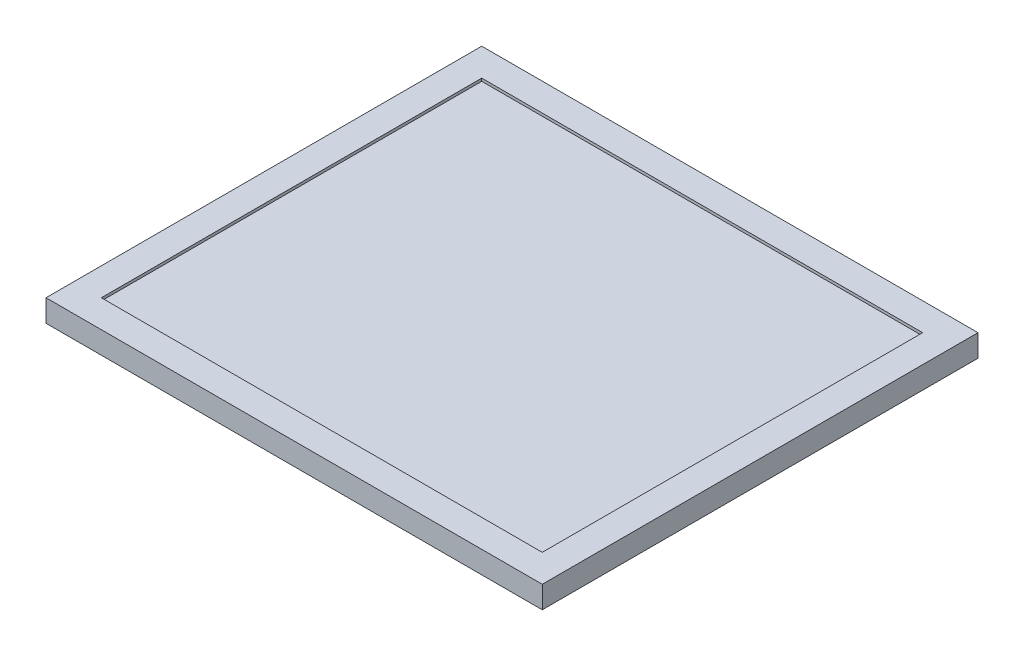
SolidWorks part; units mm, degrees
ref_plane "Front" through (0, 0, 0) normal (0, 0, 1) x (1, 0, 0)
ref_plane "Top" through (0, 0, 0) normal (0, 1, 0) x (1, 0, 0)
ref_plane "Right" through (0, 0, 0) normal (1, 0, 0) x (0, 0, -1)
sketch "Sketch1" plane through (0, 0, 0) normal (0, 1, 0) x (1, 0, 0)
  line L0 (-328.7092, 295) -> (-338.75, 284.9592)
  line L1 (348.75, 305) -> (-348.75, 305)
  line L2 (348.75, 305) -> (348.75, -305)
  line L4 (-348.75, 305) -> (-348.75, -305)
  line L5 (0, -305) -> (0, 305) construction
  line L6 (348.75, 0) -> (-348.75, 0) construction
  line L7 (-328.7092, 295) -> (-318.7092, 295)
  line L8 (-338.75, 284.9592) -> (-338.75, 227.4386)
  line L9 (-329.0717, 217.7603) -> (-318.7092, 217.7603)
  line L10 (-256.2915, 285.3217) -> (-256.2915, 227.4386)
  line L11 (-265.9698, 295) -> (-256.2915, 285.3217)
  line L12 (-256.2915, 227.4386) -> (-265.9698, 217.7603)
  line L13 (-338.75, 227.4386) -> (-329.0717, 217.7603)
  line L14 (-297.5208, 295) -> (-297.5208, 217.7603) construction
  line L15 (-318.7092, 295) -> (-318.7092, 217.7603)
  line L16 (-315.7092, 295) -> (-315.7092, 217.7603)
  line L17 (-276.3323, 295) -> (-276.3323, 217.7603)
  line L18 (-279.3323, 295) -> (-279.3323, 217.7603)
  line L19 (-315.7092, 295) -> (-279.3323, 295)
  line L20 (-276.3323, 295) -> (-265.9698, 295)
  line L21 (-276.3323, 217.7603) -> (-265.9698, 217.7603)
  line L22 (-315.7092, 217.7603) -> (-279.3323, 217.7603)
  line L23 (-253.75, 284.9592) -> (-253.75, 227.4386)
  line L24 (-253.75, 227.4386) -> (-244.0717, 217.7603)
  line L25 (-244.0717, 217.7603) -> (-233.7092, 217.7603)
  line L26 (-233.7092, 295) -> (-233.7092, 217.7603)
  line L27 (-243.7092, 295) -> (-233.7092, 295)
  line L28 (-243.7092, 295) -> (-253.75, 284.9592)
  line L29 (-194.3323, 295) -> (-194.3323, 217.7603)
  line L30 (-230.7092, 217.7603) -> (-194.3323, 217.7603)
  line L31 (-230.7092, 295) -> (-230.7092, 217.7603)
  line L32 (-230.7092, 295) -> (-194.3323, 295)
  line L33 (-191.3323, 295) -> (-191.3323, 217.7603)
  line L34 (-191.3323, 217.7603) -> (-180.9698, 217.7603)
  line L35 (-171.2915, 227.4386) -> (-180.9698, 217.7603)
  line L36 (-171.2915, 285.3217) -> (-171.2915, 227.4386)
  line L37 (-180.9698, 295) -> (-171.2915, 285.3217)
  line L38 (-191.3323, 295) -> (-180.9698, 295)
  line L39 (-168.75, 284.9592) -> (-168.75, 227.4386)
  line L40 (-168.75, 227.4386) -> (-159.0717, 217.7603)
  line L41 (-159.0717, 217.7603) -> (-148.7092, 217.7603)
  line L42 (-148.7092, 295) -> (-148.7092, 217.7603)
  line L43 (-158.7092, 295) -> (-148.7092, 295)
  line L44 (-158.7092, 295) -> (-168.75, 284.9592)
  line L45 (-109.3323, 295) -> (-109.3323, 217.7603)
  line L46 (-145.7092, 217.7603) -> (-109.3323, 217.7603)
  line L47 (-145.7092, 295) -> (-145.7092, 217.7603)
  line L48 (-145.7092, 295) -> (-109.3323, 295)
  line L49 (-106.3323, 295) -> (-106.3323, 217.7603)
  line L50 (-106.3323, 217.7603) -> (-95.9698, 217.7603)
  line L51 (-86.2915, 227.4386) -> (-95.9698, 217.7603)
  line L52 (-86.2915, 285.3217) -> (-86.2915, 227.4386)
  line L53 (-95.9698, 295) -> (-86.2915, 285.3217)
  line L54 (-106.3323, 295) -> (-95.9698, 295)
  line L55 (-83.75, 284.9592) -> (-83.75, 227.4386)
  line L56 (-83.75, 227.4386) -> (-74.0717, 217.7603)
  line L57 (-74.0717, 217.7603) -> (-63.7092, 217.7603)
  line L58 (-63.7092, 295) -> (-63.7092, 217.7603)
  line L59 (-73.7092, 295) -> (-63.7092, 295)
  line L60 (-73.7092, 295) -> (-83.75, 284.9592)
  line L61 (-24.3323, 295) -> (-24.3323, 217.7603)
  line L62 (-60.7092, 217.7603) -> (-24.3323, 217.7603)
  line L63 (-60.7092, 295) -> (-60.7092, 217.7603)
  line L64 (-60.7092, 295) -> (-24.3323, 295)
  line L65 (-21.3323, 295) -> (-21.3323, 217.7603)
  line L66 (-21.3323, 217.7603) -> (-10.9698, 217.7603)
  line L67 (-1.2915, 227.4386) -> (-10.9698, 217.7603)
  line L68 (-1.2915, 285.3217) -> (-1.2915, 227.4386)
  line L69 (-10.9698, 295) -> (-1.2915, 285.3217)
  line L70 (-21.3323, 295) -> (-10.9698, 295)
  line L71 (1.25, 284.9592) -> (1.25, 227.4386)
  line L72 (1.25, 227.4386) -> (10.9283, 217.7603)
  line L73 (10.9283, 217.7603) -> (21.2908, 217.7603)
  line L74 (21.2908, 295) -> (21.2908, 217.7603)
  line L75 (11.2908, 295) -> (21.2908, 295)
  line L76 (11.2908, 295) -> (1.25, 284.9592)
  line L77 (60.6677, 295) -> (60.6677, 217.7603)
  line L78 (24.2908, 217.7603) -> (60.6677, 217.7603)
  line L79 (24.2908, 295) -> (24.2908, 217.7603)
  line L80 (24.2908, 295) -> (60.6677, 295)
  line L81 (63.6677, 295) -> (63.6677, 217.7603)
  line L82 (63.6677, 217.7603) -> (74.0302, 217.7603)
  line L83 (83.7085, 227.4386) -> (74.0302, 217.7603)
  line L84 (83.7085, 285.3217) -> (83.7085, 227.4386)
  line L85 (74.0302, 295) -> (83.7085, 285.3217)
  line L86 (63.6677, 295) -> (74.0302, 295)
  line L87 (86.25, 284.9592) -> (86.25, 227.4386)
  line L88 (86.25, 227.4386) -> (95.9283, 217.7603)
  line L89 (95.9283, 217.7603) -> (106.2908, 217.7603)
  line L90 (106.2908, 295) -> (106.2908, 217.7603)
  line L91 (96.2908, 295) -> (106.2908, 295)
  line L92 (96.2908, 295) -> (86.25, 284.9592)
  line L93 (145.6677, 295) -> (145.6677, 217.7603)
  line L94 (109.2908, 217.7603) -> (145.6677, 217.7603)
  line L95 (109.2908, 295) -> (109.2908, 217.7603)
  line L96 (109.2908, 295) -> (145.6677, 295)
  line L97 (148.6677, 295) -> (148.6677, 217.7603)
  line L98 (148.6677, 217.7603) -> (159.0302, 217.7603)
  line L99 (168.7085, 227.4386) -> (159.0302, 217.7603)
  line L100 (168.7085, 285.3217) -> (168.7085, 227.4386)
  line L101 (159.0302, 295) -> (168.7085, 285.3217)
  line L102 (148.6677, 295) -> (159.0302, 295)
  line L103 (171.25, 284.9592) -> (171.25, 227.4386)
  line L104 (171.25, 227.4386) -> (180.9283, 217.7603)
  line L105 (180.9283, 217.7603) -> (191.2908, 217.7603)
  line L106 (191.2908, 295) -> (191.2908, 217.7603)
  line L107 (181.2908, 295) -> (191.2908, 295)
  line L108 (181.2908, 295) -> (171.25, 284.9592)
  line L109 (230.6677, 295) -> (230.6677, 217.7603)
  line L110 (194.2908, 217.7603) -> (230.6677, 217.7603)
  line L111 (194.2908, 295) -> (194.2908, 217.7603)
  line L112 (194.2908, 295) -> (230.6677, 295)
  line L113 (233.6677, 295) -> (233.6677, 217.7603)
  line L114 (233.6677, 217.7603) -> (244.0302, 217.7603)
  line L115 (253.7085, 227.4386) -> (244.0302, 217.7603)
  line L116 (253.7085, 285.3217) -> (253.7085, 227.4386)
  line L117 (244.0302, 295) -> (253.7085, 285.3217)
  line L118 (233.6677, 295) -> (244.0302, 295)
  line L119 (256.25, 284.9592) -> (256.25, 227.4386)
  line L120 (256.25, 227.4386) -> (265.9283, 217.7603)
  line L121 (265.9283, 217.7603) -> (276.2908, 217.7603)
  line L122 (276.2908, 295) -> (276.2908, 217.7603)
  line L123 (266.2908, 295) -> (276.2908, 295)
  line L124 (266.2908, 295) -> (256.25, 284.9592)
  line L125 (315.6677, 295) -> (315.6677, 217.7603)
  line L126 (279.2908, 217.7603) -> (315.6677, 217.7603)
  line L127 (279.2908, 295) -> (279.2908, 217.7603)
  line L128 (279.2908, 295) -> (315.6677, 295)
  line L129 (318.6677, 295) -> (318.6677, 217.7603)
  line L130 (318.6677, 217.7603) -> (329.0302, 217.7603)
  line L131 (338.7085, 227.4386) -> (329.0302, 217.7603)
  line L132 (338.7085, 285.3217) -> (338.7085, 227.4386)
  line L133 (329.0302, 295) -> (338.7085, 285.3217)
  line L134 (318.6677, 295) -> (329.0302, 295)
  line L135 (-253.75, 199.9592) -> (-253.75, 142.4386)
  line L136 (-253.75, 142.4386) -> (-244.0717, 132.7603)
  line L137 (-244.0717, 132.7603) -> (-233.7092, 132.7603)
  line L138 (-233.7092, 210) -> (-233.7092, 132.7603)
  line L139 (-243.7092, 210) -> (-233.7092, 210)
  line L140 (-243.7092, 210) -> (-253.75, 199.9592)
  line L141 (-194.3323, 210) -> (-194.3323, 132.7603)
  line L142 (-230.7092, 132.7603) -> (-194.3323, 132.7603)
  line L143 (-230.7092, 210) -> (-230.7092, 132.7603)
  line L144 (-230.7092, 210) -> (-194.3323, 210)
  line L145 (-191.3323, 210) -> (-191.3323, 132.7603)
  line L146 (-191.3323, 132.7603) -> (-180.9698, 132.7603)
  line L147 (-171.2915, 142.4386) -> (-180.9698, 132.7603)
  line L148 (-171.2915, 200.3217) -> (-171.2915, 142.4386)
  line L149 (-180.9698, 210) -> (-171.2915, 200.3217)
  line L150 (-191.3323, 210) -> (-180.9698, 210)
  line L151 (-168.75, 199.9592) -> (-168.75, 142.4386)
  line L152 (-168.75, 142.4386) -> (-159.0717, 132.7603)
  line L153 (-159.0717, 132.7603) -> (-148.7092, 132.7603)
  line L154 (-148.7092, 210) -> (-148.7092, 132.7603)
  line L155 (-158.7092, 210) -> (-148.7092, 210)
  line L156 (-158.7092, 210) -> (-168.75, 199.9592)
  line L157 (-109.3323, 210) -> (-109.3323, 132.7603)
  line L158 (-145.7092, 132.7603) -> (-109.3323, 132.7603)
  line L159 (-145.7092, 210) -> (-145.7092, 132.7603)
  line L160 (-145.7092, 210) -> (-109.3323, 210)
  line L161 (-106.3323, 210) -> (-106.3323, 132.7603)
  line L162 (-106.3323, 132.7603) -> (-95.9698, 132.7603)
  line L163 (-86.2915, 142.4386) -> (-95.9698, 132.7603)
  line L164 (-86.2915, 200.3217) -> (-86.2915, 142.4386)
  line L165 (-95.9698, 210) -> (-86.2915, 200.3217)
  line L166 (-106.3323, 210) -> (-95.9698, 210)
  line L167 (-83.75, 199.9592) -> (-83.75, 142.4386)
  line L168 (-83.75, 142.4386) -> (-74.0717, 132.7603)
  line L169 (-74.0717, 132.7603) -> (-63.7092, 132.7603)
  line L170 (-63.7092, 210) -> (-63.7092, 132.7603)
  line L171 (-73.7092, 210) -> (-63.7092, 210)
  line L172 (-73.7092, 210) -> (-83.75, 199.9592)
  line L173 (-24.3323, 210) -> (-24.3323, 132.7603)
  line L174 (-60.7092, 132.7603) -> (-24.3323, 132.7603)
  line L175 (-60.7092, 210) -> (-60.7092, 132.7603)
  line L176 (-60.7092, 210) -> (-24.3323, 210)
  line L177 (-21.3323, 210) -> (-21.3323, 132.7603)
  line L178 (-21.3323, 132.7603) -> (-10.9698, 132.7603)
  line L179 (-1.2915, 142.4386) -> (-10.9698, 132.7603)
  line L180 (-1.2915, 200.3217) -> (-1.2915, 142.4386)
  line L181 (-10.9698, 210) -> (-1.2915, 200.3217)
  line L182 (-21.3323, 210) -> (-10.9698, 210)
  line L183 (1.25, 199.9592) -> (1.25, 142.4386)
  line L184 (1.25, 142.4386) -> (10.9283, 132.7603)
  line L185 (10.9283, 132.7603) -> (21.2908, 132.7603)
  line L186 (21.2908, 210) -> (21.2908, 132.7603)
  line L187 (11.2908, 210) -> (21.2908, 210)
  line L188 (11.2908, 210) -> (1.25, 199.9592)
  line L189 (60.6677, 210) -> (60.6677, 132.7603)
  line L190 (24.2908, 132.7603) -> (60.6677, 132.7603)
  line L191 (24.2908, 210) -> (24.2908, 132.7603)
  line L192 (24.2908, 210) -> (60.6677, 210)
  line L193 (63.6677, 210) -> (63.6677, 132.7603)
  line L194 (63.6677, 132.7603) -> (74.0302, 132.7603)
  line L195 (83.7085, 142.4386) -> (74.0302, 132.7603)
  line L196 (83.7085, 200.3217) -> (83.7085, 142.4386)
  line L197 (74.0302, 210) -> (83.7085, 200.3217)
  line L198 (63.6677, 210) -> (74.0302, 210)
  line L199 (86.25, 199.9592) -> (86.25, 142.4386)
  line L200 (86.25, 142.4386) -> (95.9283, 132.7603)
  line L201 (95.9283, 132.7603) -> (106.2908, 132.7603)
  line L202 (106.2908, 210) -> (106.2908, 132.7603)
  line L203 (96.2908, 210) -> (106.2908, 210)
  line L204 (96.2908, 210) -> (86.25, 199.9592)
  line L205 (145.6677, 210) -> (145.6677, 132.7603)
  line L206 (109.2908, 132.7603) -> (145.6677, 132.7603)
  line L207 (109.2908, 210) -> (109.2908, 132.7603)
  line L208 (109.2908, 210) -> (145.6677, 210)
  line L209 (148.6677, 210) -> (148.6677, 132.7603)
  line L210 (148.6677, 132.7603) -> (159.0302, 132.7603)
  line L211 (168.7085, 142.4386) -> (159.0302, 132.7603)
  line L212 (168.7085, 200.3217) -> (168.7085, 142.4386)
  line L213 (159.0302, 210) -> (168.7085, 200.3217)
  line L214 (148.6677, 210) -> (159.0302, 210)
  line L215 (171.25, 199.9592) -> (171.25, 142.4386)
  line L216 (171.25, 142.4386) -> (180.9283, 132.7603)
  line L217 (180.9283, 132.7603) -> (191.2908, 132.7603)
  line L218 (191.2908, 210) -> (191.2908, 132.7603)
  line L219 (181.2908, 210) -> (191.2908, 210)
  line L220 (181.2908, 210) -> (171.25, 199.9592)
  line L221 (230.6677, 210) -> (230.6677, 132.7603)
  line L222 (194.2908, 132.7603) -> (230.6677, 132.7603)
  line L223 (194.2908, 210) -> (194.2908, 132.7603)
  line L224 (194.2908, 210) -> (230.6677, 210)
  line L225 (233.6677, 210) -> (233.6677, 132.7603)
  line L226 (233.6677, 132.7603) -> (244.0302, 132.7603)
  line L227 (253.7085, 142.4386) -> (244.0302, 132.7603)
  line L228 (253.7085, 200.3217) -> (253.7085, 142.4386)
  line L229 (244.0302, 210) -> (253.7085, 200.3217)
  line L230 (233.6677, 210) -> (244.0302, 210)
  line L231 (256.25, 199.9592) -> (256.25, 142.4386)
  line L232 (256.25, 142.4386) -> (265.9283, 132.7603)
  line L233 (265.9283, 132.7603) -> (276.2908, 132.7603)
  line L234 (276.2908, 210) -> (276.2908, 132.7603)
  line L235 (266.2908, 210) -> (276.2908, 210)
  line L236 (266.2908, 210) -> (256.25, 199.9592)
  line L237 (315.6677, 210) -> (315.6677, 132.7603)
  line L238 (279.2908, 132.7603) -> (315.6677, 132.7603)
  line L239 (279.2908, 210) -> (279.2908, 132.7603)
  line L240 (279.2908, 210) -> (315.6677, 210)
  line L241 (318.6677, 210) -> (318.6677, 132.7603)
  line L242 (318.6677, 132.7603) -> (329.0302, 132.7603)
  line L243 (338.7085, 142.4386) -> (329.0302, 132.7603)
  line L244 (338.7085, 200.3217) -> (338.7085, 142.4386)
  line L245 (329.0302, 210) -> (338.7085, 200.3217)
  line L246 (318.6677, 210) -> (329.0302, 210)
  line L247 (-253.75, 114.9592) -> (-253.75, 57.4386)
  line L248 (-253.75, 57.4386) -> (-244.0717, 47.7603)
  line L249 (-244.0717, 47.7603) -> (-233.7092, 47.7603)
  line L250 (-233.7092, 125) -> (-233.7092, 47.7603)
  line L251 (-243.7092, 125) -> (-233.7092, 125)
  line L252 (-243.7092, 125) -> (-253.75, 114.9592)
  line L253 (-194.3323, 125) -> (-194.3323, 47.7603)
  line L254 (-230.7092, 47.7603) -> (-194.3323, 47.7603)
  line L255 (-230.7092, 125) -> (-230.7092, 47.7603)
  line L256 (-230.7092, 125) -> (-194.3323, 125)
  line L257 (-191.3323, 125) -> (-191.3323, 47.7603)
  line L258 (-191.3323, 47.7603) -> (-180.9698, 47.7603)
  line L259 (-171.2915, 57.4386) -> (-180.9698, 47.7603)
  line L260 (-171.2915, 115.3217) -> (-171.2915, 57.4386)
  line L261 (-180.9698, 125) -> (-171.2915, 115.3217)
  line L262 (-191.3323, 125) -> (-180.9698, 125)
  line L263 (-168.75, 114.9592) -> (-168.75, 57.4386)
  line L264 (-168.75, 57.4386) -> (-159.0717, 47.7603)
  line L265 (-159.0717, 47.7603) -> (-148.7092, 47.7603)
  line L266 (-148.7092, 125) -> (-148.7092, 47.7603)
  line L267 (-158.7092, 125) -> (-148.7092, 125)
  line L268 (-158.7092, 125) -> (-168.75, 114.9592)
  line L269 (-109.3323, 125) -> (-109.3323, 47.7603)
  line L270 (-145.7092, 47.7603) -> (-109.3323, 47.7603)
  line L271 (-145.7092, 125) -> (-145.7092, 47.7603)
  line L272 (-145.7092, 125) -> (-109.3323, 125)
  line L273 (-106.3323, 125) -> (-106.3323, 47.7603)
  line L274 (-106.3323, 47.7603) -> (-95.9698, 47.7603)
  line L275 (-86.2915, 57.4386) -> (-95.9698, 47.7603)
  line L276 (-86.2915, 115.3217) -> (-86.2915, 57.4386)
  line L277 (-95.9698, 125) -> (-86.2915, 115.3217)
  line L278 (-106.3323, 125) -> (-95.9698, 125)
  line L279 (-83.75, 114.9592) -> (-83.75, 57.4386)
  line L280 (-83.75, 57.4386) -> (-74.0717, 47.7603)
  line L281 (-74.0717, 47.7603) -> (-63.7092, 47.7603)
  line L282 (-63.7092, 125) -> (-63.7092, 47.7603)
  line L283 (-73.7092, 125) -> (-63.7092, 125)
  line L284 (-73.7092, 125) -> (-83.75, 114.9592)
  line L285 (-24.3323, 125) -> (-24.3323, 47.7603)
  line L286 (-60.7092, 47.7603) -> (-24.3323, 47.7603)
  line L287 (-60.7092, 125) -> (-60.7092, 47.7603)
  line L288 (-60.7092, 125) -> (-24.3323, 125)
  line L289 (-21.3323, 125) -> (-21.3323, 47.7603)
  line L290 (-21.3323, 47.7603) -> (-10.9698, 47.7603)
  line L291 (-1.2915, 57.4386) -> (-10.9698, 47.7603)
  line L292 (-1.2915, 115.3217) -> (-1.2915, 57.4386)
  line L293 (-10.9698, 125) -> (-1.2915, 115.3217)
  line L294 (-21.3323, 125) -> (-10.9698, 125)
  line L295 (1.25, 114.9592) -> (1.25, 57.4386)
  line L296 (1.25, 57.4386) -> (10.9283, 47.7603)
  line L297 (10.9283, 47.7603) -> (21.2908, 47.7603)
  line L298 (21.2908, 125) -> (21.2908, 47.7603)
  line L299 (11.2908, 125) -> (21.2908, 125)
  line L300 (11.2908, 125) -> (1.25, 114.9592)
  line L301 (60.6677, 125) -> (60.6677, 47.7603)
  line L302 (24.2908, 47.7603) -> (60.6677, 47.7603)
  line L303 (24.2908, 125) -> (24.2908, 47.7603)
  line L304 (24.2908, 125) -> (60.6677, 125)
  line L305 (63.6677, 125) -> (63.6677, 47.7603)
  line L306 (63.6677, 47.7603) -> (74.0302, 47.7603)
  line L307 (83.7085, 57.4386) -> (74.0302, 47.7603)
  line L308 (83.7085, 115.3217) -> (83.7085, 57.4386)
  line L309 (74.0302, 125) -> (83.7085, 115.3217)
  line L310 (63.6677, 125) -> (74.0302, 125)
  line L311 (86.25, 114.9592) -> (86.25, 57.4386)
  line L312 (86.25, 57.4386) -> (95.9283, 47.7603)
  line L313 (95.9283, 47.7603) -> (106.2908, 47.7603)
  line L314 (106.2908, 125) -> (106.2908, 47.7603)
  line L315 (96.2908, 125) -> (106.2908, 125)
  line L316 (96.2908, 125) -> (86.25, 114.9592)
  line L317 (145.6677, 125) -> (145.6677, 47.7603)
  line L318 (109.2908, 47.7603) -> (145.6677, 47.7603)
  line L319 (109.2908, 125) -> (109.2908, 47.7603)
  line L320 (109.2908, 125) -> (145.6677, 125)
  line L321 (148.6677, 125) -> (148.6677, 47.7603)
  line L322 (148.6677, 47.7603) -> (159.0302, 47.7603)
  line L323 (168.7085, 57.4386) -> (159.0302, 47.7603)
  line L324 (168.7085, 115.3217) -> (168.7085, 57.4386)
  line L325 (159.0302, 125) -> (168.7085, 115.3217)
  line L326 (148.6677, 125) -> (159.0302, 125)
  line L327 (171.25, 114.9592) -> (171.25, 57.4386)
  line L328 (171.25, 57.4386) -> (180.9283, 47.7603)
  line L329 (180.9283, 47.7603) -> (191.2908, 47.7603)
  line L330 (191.2908, 125) -> (191.2908, 47.7603)
  line L331 (181.2908, 125) -> (191.2908, 125)
  line L332 (181.2908, 125) -> (171.25, 114.9592)
  line L333 (230.6677, 125) -> (230.6677, 47.7603)
  line L334 (194.2908, 47.7603) -> (230.6677, 47.7603)
  line L335 (194.2908, 125) -> (194.2908, 47.7603)
  line L336 (194.2908, 125) -> (230.6677, 125)
  line L337 (233.6677, 125) -> (233.6677, 47.7603)
  line L338 (233.6677, 47.7603) -> (244.0302, 47.7603)
  line L339 (253.7085, 57.4386) -> (244.0302, 47.7603)
  line L340 (253.7085, 115.3217) -> (253.7085, 57.4386)
  line L341 (244.0302, 125) -> (253.7085, 115.3217)
  line L342 (233.6677, 125) -> (244.0302, 125)
  line L343 (256.25, 114.9592) -> (256.25, 57.4386)
  line L344 (256.25, 57.4386) -> (265.9283, 47.7603)
  line L345 (265.9283, 47.7603) -> (276.2908, 47.7603)
  line L346 (276.2908, 125) -> (276.2908, 47.7603)
  line L347 (266.2908, 125) -> (276.2908, 125)
  line L348 (266.2908, 125) -> (256.25, 114.9592)
  line L349 (315.6677, 125) -> (315.6677, 47.7603)
  line L350 (279.2908, 47.7603) -> (315.6677, 47.7603)
  line L351 (279.2908, 125) -> (279.2908, 47.7603)
  line L352 (279.2908, 125) -> (315.6677, 125)
  line L353 (318.6677, 125) -> (318.6677, 47.7603)
  line L354 (318.6677, 47.7603) -> (329.0302, 47.7603)
  line L355 (338.7085, 57.4386) -> (329.0302, 47.7603)
  line L356 (338.7085, 115.3217) -> (338.7085, 57.4386)
  line L357 (329.0302, 125) -> (338.7085, 115.3217)
  line L358 (318.6677, 125) -> (329.0302, 125)
  line L359 (-253.75, 29.9592) -> (-253.75, -27.5614)
  line L360 (-253.75, -27.5614) -> (-244.0717, -37.2397)
  line L361 (-244.0717, -37.2397) -> (-233.7092, -37.2397)
  line L362 (-233.7092, 40) -> (-233.7092, -37.2397)
  line L363 (-243.7092, 40) -> (-233.7092, 40)
  line L364 (-243.7092, 40) -> (-253.75, 29.9592)
  line L365 (-194.3323, 40) -> (-194.3323, -37.2397)
  line L366 (-230.7092, -37.2397) -> (-194.3323, -37.2397)
  line L367 (-230.7092, 40) -> (-230.7092, -37.2397)
  line L368 (-230.7092, 40) -> (-194.3323, 40)
  line L369 (-191.3323, 40) -> (-191.3323, -37.2397)
  line L370 (-191.3323, -37.2397) -> (-180.9698, -37.2397)
  line L371 (-171.2915, -27.5614) -> (-180.9698, -37.2397)
  line L372 (-171.2915, 30.3217) -> (-171.2915, -27.5614)
  line L373 (-180.9698, 40) -> (-171.2915, 30.3217)
  line L374 (-191.3323, 40) -> (-180.9698, 40)
  line L375 (-168.75, 29.9592) -> (-168.75, -27.5614)
  line L376 (-168.75, -27.5614) -> (-159.0717, -37.2397)
  line L377 (-159.0717, -37.2397) -> (-148.7092, -37.2397)
  line L378 (-148.7092, 40) -> (-148.7092, -37.2397)
  line L379 (-158.7092, 40) -> (-148.7092, 40)
  line L380 (-158.7092, 40) -> (-168.75, 29.9592)
  line L381 (-109.3323, 40) -> (-109.3323, -37.2397)
  line L382 (-145.7092, -37.2397) -> (-109.3323, -37.2397)
  line L383 (-145.7092, 40) -> (-145.7092, -37.2397)
  line L384 (-145.7092, 40) -> (-109.3323, 40)
  line L385 (-106.3323, 40) -> (-106.3323, -37.2397)
  line L386 (-106.3323, -37.2397) -> (-95.9698, -37.2397)
  line L387 (-86.2915, -27.5614) -> (-95.9698, -37.2397)
  line L388 (-86.2915, 30.3217) -> (-86.2915, -27.5614)
  line L389 (-95.9698, 40) -> (-86.2915, 30.3217)
  line L390 (-106.3323, 40) -> (-95.9698, 40)
  line L391 (-83.75, 29.9592) -> (-83.75, -27.5614)
  line L392 (-83.75, -27.5614) -> (-74.0717, -37.2397)
  line L393 (-74.0717, -37.2397) -> (-63.7092, -37.2397)
  line L394 (-63.7092, 40) -> (-63.7092, -37.2397)
  line L395 (-73.7092, 40) -> (-63.7092, 40)
  line L396 (-73.7092, 40) -> (-83.75, 29.9592)
  line L397 (-24.3323, 40) -> (-24.3323, -37.2397)
  line L398 (-60.7092, -37.2397) -> (-24.3323, -37.2397)
  line L399 (-60.7092, 40) -> (-60.7092, -37.2397)
  line L400 (-60.7092, 40) -> (-24.3323, 40)
  line L401 (-21.3323, 40) -> (-21.3323, -37.2397)
  line L402 (-21.3323, -37.2397) -> (-10.9698, -37.2397)
  line L403 (-1.2915, -27.5614) -> (-10.9698, -37.2397)
  line L404 (-1.2915, 30.3217) -> (-1.2915, -27.5614)
  line L405 (-10.9698, 40) -> (-1.2915, 30.3217)
  line L406 (-21.3323, 40) -> (-10.9698, 40)
  line L407 (1.25, 29.9592) -> (1.25, -27.5614)
  line L408 (1.25, -27.5614) -> (10.9283, -37.2397)
  line L409 (10.9283, -37.2397) -> (21.2908, -37.2397)
  line L410 (21.2908, 40) -> (21.2908, -37.2397)
  line L411 (11.2908, 40) -> (21.2908, 40)
  line L412 (11.2908, 40) -> (1.25, 29.9592)
  line L413 (60.6677, 40) -> (60.6677, -37.2397)
  line L414 (24.2908, -37.2397) -> (60.6677, -37.2397)
  line L415 (24.2908, 40) -> (24.2908, -37.2397)
  line L416 (24.2908, 40) -> (60.6677, 40)
  line L417 (63.6677, 40) -> (63.6677, -37.2397)
  line L418 (63.6677, -37.2397) -> (74.0302, -37.2397)
  line L419 (83.7085, -27.5614) -> (74.0302, -37.2397)
  line L420 (83.7085, 30.3217) -> (83.7085, -27.5614)
  line L421 (74.0302, 40) -> (83.7085, 30.3217)
  line L422 (63.6677, 40) -> (74.0302, 40)
  line L423 (86.25, 29.9592) -> (86.25, -27.5614)
  line L424 (86.25, -27.5614) -> (95.9283, -37.2397)
  line L425 (95.9283, -37.2397) -> (106.2908, -37.2397)
  line L426 (106.2908, 40) -> (106.2908, -37.2397)
  line L427 (96.2908, 40) -> (106.2908, 40)
  line L428 (96.2908, 40) -> (86.25, 29.9592)
  line L429 (145.6677, 40) -> (145.6677, -37.2397)
  line L430 (109.2908, -37.2397) -> (145.6677, -37.2397)
  line L431 (109.2908, 40) -> (109.2908, -37.2397)
  line L432 (109.2908, 40) -> (145.6677, 40)
  line L433 (148.6677, 40) -> (148.6677, -37.2397)
  line L434 (148.6677, -37.2397) -> (159.0302, -37.2397)
  line L435 (168.7085, -27.5614) -> (159.0302, -37.2397)
  line L436 (168.7085, 30.3217) -> (168.7085, -27.5614)
  line L437 (159.0302, 40) -> (168.7085, 30.3217)
  line L438 (148.6677, 40) -> (159.0302, 40)
  line L439 (171.25, 29.9592) -> (171.25, -27.5614)
  line L440 (171.25, -27.5614) -> (180.9283, -37.2397)
  line L441 (180.9283, -37.2397) -> (191.2908, -37.2397)
  line L442 (191.2908, 40) -> (191.2908, -37.2397)
  line L443 (181.2908, 40) -> (191.2908, 40)
  line L444 (181.2908, 40) -> (171.25, 29.9592)
  line L445 (230.6677, 40) -> (230.6677, -37.2397)
  line L446 (194.2908, -37.2397) -> (230.6677, -37.2397)
  line L447 (194.2908, 40) -> (194.2908, -37.2397)
  line L448 (194.2908, 40) -> (230.6677, 40)
  line L449 (233.6677, 40) -> (233.6677, -37.2397)
  line L450 (233.6677, -37.2397) -> (244.0302, -37.2397)
  line L451 (253.7085, -27.5614) -> (244.0302, -37.2397)
  line L452 (253.7085, 30.3217) -> (253.7085, -27.5614)
  line L453 (244.0302, 40) -> (253.7085, 30.3217)
  line L454 (233.6677, 40) -> (244.0302, 40)
  line L455 (256.25, 29.9592) -> (256.25, -27.5614)
  line L456 (256.25, -27.5614) -> (265.9283, -37.2397)
  line L457 (265.9283, -37.2397) -> (276.2908, -37.2397)
  line L458 (276.2908, 40) -> (276.2908, -37.2397)
  line L459 (266.2908, 40) -> (276.2908, 40)
  line L460 (266.2908, 40) -> (256.25, 29.9592)
  line L461 (315.6677, 40) -> (315.6677, -37.2397)
  line L462 (279.2908, -37.2397) -> (315.6677, -37.2397)
  line L463 (279.2908, 40) -> (279.2908, -37.2397)
  line L464 (279.2908, 40) -> (315.6677, 40)
  line L465 (318.6677, 40) -> (318.6677, -37.2397)
  line L466 (318.6677, -37.2397) -> (329.0302, -37.2397)
  line L467 (338.7085, -27.5614) -> (329.0302, -37.2397)
  line L468 (338.7085, 30.3217) -> (338.7085, -27.5614)
  line L469 (329.0302, 40) -> (338.7085, 30.3217)
  line L470 (318.6677, 40) -> (329.0302, 40)
  line L471 (-253.75, -55.0408) -> (-253.75, -112.5614)
  line L472 (-253.75, -112.5614) -> (-244.0717, -122.2397)
  line L473 (-244.0717, -122.2397) -> (-233.7092, -122.2397)
  line L474 (-233.7092, -45) -> (-233.7092, -122.2397)
  line L475 (-243.7092, -45) -> (-233.7092, -45)
  line L476 (-243.7092, -45) -> (-253.75, -55.0408)
  line L477 (-194.3323, -45) -> (-194.3323, -122.2397)
  line L478 (-230.7092, -122.2397) -> (-194.3323, -122.2397)
  line L479 (-230.7092, -45) -> (-230.7092, -122.2397)
  line L480 (-230.7092, -45) -> (-194.3323, -45)
  line L481 (-191.3323, -45) -> (-191.3323, -122.2397)
  line L482 (-191.3323, -122.2397) -> (-180.9698, -122.2397)
  line L483 (-171.2915, -112.5614) -> (-180.9698, -122.2397)
  line L484 (-171.2915, -54.6783) -> (-171.2915, -112.5614)
  line L485 (-180.9698, -45) -> (-171.2915, -54.6783)
  line L486 (-191.3323, -45) -> (-180.9698, -45)
  line L487 (-168.75, -55.0408) -> (-168.75, -112.5614)
  line L488 (-168.75, -112.5614) -> (-159.0717, -122.2397)
  line L489 (-159.0717, -122.2397) -> (-148.7092, -122.2397)
  line L490 (-148.7092, -45) -> (-148.7092, -122.2397)
  line L491 (-158.7092, -45) -> (-148.7092, -45)
  line L492 (-158.7092, -45) -> (-168.75, -55.0408)
  line L493 (-109.3323, -45) -> (-109.3323, -122.2397)
  line L494 (-145.7092, -122.2397) -> (-109.3323, -122.2397)
  line L495 (-145.7092, -45) -> (-145.7092, -122.2397)
  line L496 (-145.7092, -45) -> (-109.3323, -45)
  line L497 (-106.3323, -45) -> (-106.3323, -122.2397)
  line L498 (-106.3323, -122.2397) -> (-95.9698, -122.2397)
  line L499 (-86.2915, -112.5614) -> (-95.9698, -122.2397)
  line L500 (-86.2915, -54.6783) -> (-86.2915, -112.5614)
  line L501 (-95.9698, -45) -> (-86.2915, -54.6783)
  line L502 (-106.3323, -45) -> (-95.9698, -45)
  line L503 (-83.75, -55.0408) -> (-83.75, -112.5614)
  line L504 (-83.75, -112.5614) -> (-74.0717, -122.2397)
  line L505 (-74.0717, -122.2397) -> (-63.7092, -122.2397)
  line L506 (-63.7092, -45) -> (-63.7092, -122.2397)
  line L507 (-73.7092, -45) -> (-63.7092, -45)
  line L508 (-73.7092, -45) -> (-83.75, -55.0408)
  line L509 (-24.3323, -45) -> (-24.3323, -122.2397)
  line L510 (-60.7092, -122.2397) -> (-24.3323, -122.2397)
  line L511 (-60.7092, -45) -> (-60.7092, -122.2397)
  line L512 (-60.7092, -45) -> (-24.3323, -45)
  line L513 (-21.3323, -45) -> (-21.3323, -122.2397)
  line L514 (-21.3323, -122.2397) -> (-10.9698, -122.2397)
  line L515 (-1.2915, -112.5614) -> (-10.9698, -122.2397)
  line L516 (-1.2915, -54.6783) -> (-1.2915, -112.5614)
  line L517 (-10.9698, -45) -> (-1.2915, -54.6783)
  line L518 (-21.3323, -45) -> (-10.9698, -45)
  line L519 (1.25, -55.0408) -> (1.25, -112.5614)
  line L520 (1.25, -112.5614) -> (10.9283, -122.2397)
  line L521 (10.9283, -122.2397) -> (21.2908, -122.2397)
  line L522 (21.2908, -45) -> (21.2908, -122.2397)
  line L523 (11.2908, -45) -> (21.2908, -45)
  line L524 (11.2908, -45) -> (1.25, -55.0408)
  line L525 (60.6677, -45) -> (60.6677, -122.2397)
  line L526 (24.2908, -122.2397) -> (60.6677, -122.2397)
  line L527 (24.2908, -45) -> (24.2908, -122.2397)
  line L528 (24.2908, -45) -> (60.6677, -45)
  line L529 (63.6677, -45) -> (63.6677, -122.2397)
  line L530 (63.6677, -122.2397) -> (74.0302, -122.2397)
  line L531 (83.7085, -112.5614) -> (74.0302, -122.2397)
  line L532 (83.7085, -54.6783) -> (83.7085, -112.5614)
  line L533 (74.0302, -45) -> (83.7085, -54.6783)
  line L534 (63.6677, -45) -> (74.0302, -45)
  line L535 (86.25, -55.0408) -> (86.25, -112.5614)
  line L536 (86.25, -112.5614) -> (95.9283, -122.2397)
  line L537 (95.9283, -122.2397) -> (106.2908, -122.2397)
  line L538 (106.2908, -45) -> (106.2908, -122.2397)
  line L539 (96.2908, -45) -> (106.2908, -45)
  line L540 (96.2908, -45) -> (86.25, -55.0408)
  line L541 (145.6677, -45) -> (145.6677, -122.2397)
  line L542 (109.2908, -122.2397) -> (145.6677, -122.2397)
  line L543 (109.2908, -45) -> (109.2908, -122.2397)
  line L544 (109.2908, -45) -> (145.6677, -45)
  line L545 (148.6677, -45) -> (148.6677, -122.2397)
  line L546 (148.6677, -122.2397) -> (159.0302, -122.2397)
  line L547 (168.7085, -112.5614) -> (159.0302, -122.2397)
  line L548 (168.7085, -54.6783) -> (168.7085, -112.5614)
  line L549 (159.0302, -45) -> (168.7085, -54.6783)
  line L550 (148.6677, -45) -> (159.0302, -45)
  line L551 (171.25, -55.0408) -> (171.25, -112.5614)
  line L552 (171.25, -112.5614) -> (180.9283, -122.2397)
  line L553 (180.9283, -122.2397) -> (191.2908, -122.2397)
  line L554 (191.2908, -45) -> (191.2908, -122.2397)
  line L555 (181.2908, -45) -> (191.2908, -45)
  line L556 (181.2908, -45) -> (171.25, -55.0408)
  line L557 (230.6677, -45) -> (230.6677, -122.2397)
  line L558 (194.2908, -122.2397) -> (230.6677, -122.2397)
  line L559 (194.2908, -45) -> (194.2908, -122.2397)
  line L560 (194.2908, -45) -> (230.6677, -45)
  line L561 (233.6677, -45) -> (233.6677, -122.2397)
  line L562 (233.6677, -122.2397) -> (244.0302, -122.2397)
  line L563 (253.7085, -112.5614) -> (244.0302, -122.2397)
  line L564 (253.7085, -54.6783) -> (253.7085, -112.5614)
  line L565 (244.0302, -45) -> (253.7085, -54.6783)
  line L566 (233.6677, -45) -> (244.0302, -45)
  line L567 (256.25, -55.0408) -> (256.25, -112.5614)
  line L568 (256.25, -112.5614) -> (265.9283, -122.2397)
  line L569 (265.9283, -122.2397) -> (276.2908, -122.2397)
  line L570 (276.2908, -45) -> (276.2908, -122.2397)
  line L571 (266.2908, -45) -> (276.2908, -45)
  line L572 (266.2908, -45) -> (256.25, -55.0408)
  line L573 (315.6677, -45) -> (315.6677, -122.2397)
  line L574 (279.2908, -122.2397) -> (315.6677, -122.2397)
  line L575 (279.2908, -45) -> (279.2908, -122.2397)
  line L576 (279.2908, -45) -> (315.6677, -45)
  line L577 (318.6677, -45) -> (318.6677, -122.2397)
  line L578 (318.6677, -122.2397) -> (329.0302, -122.2397)
  line L579 (338.7085, -112.5614) -> (329.0302, -122.2397)
  line L580 (338.7085, -54.6783) -> (338.7085, -112.5614)
  line L581 (329.0302, -45) -> (338.7085, -54.6783)
  line L582 (318.6677, -45) -> (329.0302, -45)
  line L583 (-253.75, -140.0408) -> (-253.75, -197.5614)
  line L584 (-253.75, -197.5614) -> (-244.0717, -207.2397)
  line L585 (-244.0717, -207.2397) -> (-233.7092, -207.2397)
  line L586 (-233.7092, -130) -> (-233.7092, -207.2397)
  line L587 (-243.7092, -130) -> (-233.7092, -130)
  line L588 (-243.7092, -130) -> (-253.75, -140.0408)
  line L589 (-194.3323, -130) -> (-194.3323, -207.2397)
  line L590 (-230.7092, -207.2397) -> (-194.3323, -207.2397)
  line L591 (-230.7092, -130) -> (-230.7092, -207.2397)
  line L592 (-230.7092, -130) -> (-194.3323, -130)
  line L593 (-191.3323, -130) -> (-191.3323, -207.2397)
  line L594 (-191.3323, -207.2397) -> (-180.9698, -207.2397)
  line L595 (-171.2915, -197.5614) -> (-180.9698, -207.2397)
  line L596 (-171.2915, -139.6783) -> (-171.2915, -197.5614)
  line L597 (-180.9698, -130) -> (-171.2915, -139.6783)
  line L598 (-191.3323, -130) -> (-180.9698, -130)
  line L599 (-168.75, -140.0408) -> (-168.75, -197.5614)
  line L600 (-168.75, -197.5614) -> (-159.0717, -207.2397)
  line L601 (-159.0717, -207.2397) -> (-148.7092, -207.2397)
  line L602 (-148.7092, -130) -> (-148.7092, -207.2397)
  line L603 (-158.7092, -130) -> (-148.7092, -130)
  line L604 (-158.7092, -130) -> (-168.75, -140.0408)
  line L605 (-109.3323, -130) -> (-109.3323, -207.2397)
  line L606 (-145.7092, -207.2397) -> (-109.3323, -207.2397)
  line L607 (-145.7092, -130) -> (-145.7092, -207.2397)
  line L608 (-145.7092, -130) -> (-109.3323, -130)
  line L609 (-106.3323, -130) -> (-106.3323, -207.2397)
  line L610 (-106.3323, -207.2397) -> (-95.9698, -207.2397)
  line L611 (-86.2915, -197.5614) -> (-95.9698, -207.2397)
  line L612 (-86.2915, -139.6783) -> (-86.2915, -197.5614)
  line L613 (-95.9698, -130) -> (-86.2915, -139.6783)
  line L614 (-106.3323, -130) -> (-95.9698, -130)
  line L615 (-83.75, -140.0408) -> (-83.75, -197.5614)
  line L616 (-83.75, -197.5614) -> (-74.0717, -207.2397)
  line L617 (-74.0717, -207.2397) -> (-63.7092, -207.2397)
  line L618 (-63.7092, -130) -> (-63.7092, -207.2397)
  line L619 (-73.7092, -130) -> (-63.7092, -130)
  line L620 (-73.7092, -130) -> (-83.75, -140.0408)
  line L621 (-24.3323, -130) -> (-24.3323, -207.2397)
  line L622 (-60.7092, -207.2397) -> (-24.3323, -207.2397)
  line L623 (-60.7092, -130) -> (-60.7092, -207.2397)
  line L624 (-60.7092, -130) -> (-24.3323, -130)
  line L625 (-21.3323, -130) -> (-21.3323, -207.2397)
  line L626 (-21.3323, -207.2397) -> (-10.9698, -207.2397)
  line L627 (-1.2915, -197.5614) -> (-10.9698, -207.2397)
  line L628 (-1.2915, -139.6783) -> (-1.2915, -197.5614)
  line L629 (-10.9698, -130) -> (-1.2915, -139.6783)
  line L630 (-21.3323, -130) -> (-10.9698, -130)
  line L631 (1.25, -140.0408) -> (1.25, -197.5614)
  line L632 (1.25, -197.5614) -> (10.9283, -207.2397)
  line L633 (10.9283, -207.2397) -> (21.2908, -207.2397)
  line L634 (21.2908, -130) -> (21.2908, -207.2397)
  line L635 (11.2908, -130) -> (21.2908, -130)
  line L636 (11.2908, -130) -> (1.25, -140.0408)
  line L637 (60.6677, -130) -> (60.6677, -207.2397)
  line L638 (24.2908, -207.2397) -> (60.6677, -207.2397)
  line L639 (24.2908, -130) -> (24.2908, -207.2397)
  line L640 (24.2908, -130) -> (60.6677, -130)
  line L641 (63.6677, -130) -> (63.6677, -207.2397)
  line L642 (63.6677, -207.2397) -> (74.0302, -207.2397)
  line L643 (83.7085, -197.5614) -> (74.0302, -207.2397)
  line L644 (83.7085, -139.6783) -> (83.7085, -197.5614)
  line L645 (74.0302, -130) -> (83.7085, -139.6783)
  line L646 (63.6677, -130) -> (74.0302, -130)
  line L647 (86.25, -140.0408) -> (86.25, -197.5614)
  line L648 (86.25, -197.5614) -> (95.9283, -207.2397)
  line L649 (95.9283, -207.2397) -> (106.2908, -207.2397)
  line L650 (106.2908, -130) -> (106.2908, -207.2397)
  line L651 (96.2908, -130) -> (106.2908, -130)
  line L652 (96.2908, -130) -> (86.25, -140.0408)
  line L653 (145.6677, -130) -> (145.6677, -207.2397)
  line L654 (109.2908, -207.2397) -> (145.6677, -207.2397)
  line L655 (109.2908, -130) -> (109.2908, -207.2397)
  line L656 (109.2908, -130) -> (145.6677, -130)
  line L657 (148.6677, -130) -> (148.6677, -207.2397)
  line L658 (148.6677, -207.2397) -> (159.0302, -207.2397)
  line L659 (168.7085, -197.5614) -> (159.0302, -207.2397)
  line L660 (168.7085, -139.6783) -> (168.7085, -197.5614)
  line L661 (159.0302, -130) -> (168.7085, -139.6783)
  line L662 (148.6677, -130) -> (159.0302, -130)
  line L663 (171.25, -140.0408) -> (171.25, -197.5614)
  line L664 (171.25, -197.5614) -> (180.9283, -207.2397)
  line L665 (180.9283, -207.2397) -> (191.2908, -207.2397)
  line L666 (191.2908, -130) -> (191.2908, -207.2397)
  line L667 (181.2908, -130) -> (191.2908, -130)
  line L668 (181.2908, -130) -> (171.25, -140.0408)
  line L669 (230.6677, -130) -> (230.6677, -207.2397)
  line L670 (194.2908, -207.2397) -> (230.6677, -207.2397)
  line L671 (194.2908, -130) -> (194.2908, -207.2397)
  line L672 (194.2908, -130) -> (230.6677, -130)
  line L673 (233.6677, -130) -> (233.6677, -207.2397)
  line L674 (233.6677, -207.2397) -> (244.0302, -207.2397)
  line L675 (253.7085, -197.5614) -> (244.0302, -207.2397)
  line L676 (253.7085, -139.6783) -> (253.7085, -197.5614)
  line L677 (244.0302, -130) -> (253.7085, -139.6783)
  line L678 (233.6677, -130) -> (244.0302, -130)
  line L679 (256.25, -140.0408) -> (256.25, -197.5614)
  line L680 (256.25, -197.5614) -> (265.9283, -207.2397)
  line L681 (265.9283, -207.2397) -> (276.2908, -207.2397)
  line L682 (276.2908, -130) -> (276.2908, -207.2397)
  line L683 (266.2908, -130) -> (276.2908, -130)
  line L684 (266.2908, -130) -> (256.25, -140.0408)
  line L685 (315.6677, -130) -> (315.6677, -207.2397)
  line L686 (279.2908, -207.2397) -> (315.6677, -207.2397)
  line L687 (279.2908, -130) -> (279.2908, -207.2397)
  line L688 (279.2908, -130) -> (315.6677, -130)
  line L689 (318.6677, -130) -> (318.6677, -207.2397)
  line L690 (318.6677, -207.2397) -> (329.0302, -207.2397)
  line L691 (338.7085, -197.5614) -> (329.0302, -207.2397)
  line L692 (338.7085, -139.6783) -> (338.7085, -197.5614)
  line L693 (329.0302, -130) -> (338.7085, -139.6783)
  line L694 (318.6677, -130) -> (329.0302, -130)
  line L695 (-253.75, -225.0408) -> (-253.75, -282.5614)
  line L696 (-253.75, -282.5614) -> (-244.0717, -292.2397)
  line L697 (-244.0717, -292.2397) -> (-233.7092, -292.2397)
  line L698 (-233.7092, -215) -> (-233.7092, -292.2397)
  line L699 (-243.7092, -215) -> (-233.7092, -215)
  line L700 (-243.7092, -215) -> (-253.75, -225.0408)
  line L701 (-194.3323, -215) -> (-194.3323, -292.2397)
  line L702 (-230.7092, -292.2397) -> (-194.3323, -292.2397)
  line L703 (-230.7092, -215) -> (-230.7092, -292.2397)
  line L704 (-230.7092, -215) -> (-194.3323, -215)
  line L705 (-191.3323, -215) -> (-191.3323, -292.2397)
  line L706 (-191.3323, -292.2397) -> (-180.9698, -292.2397)
  line L707 (-171.2915, -282.5614) -> (-180.9698, -292.2397)
  line L708 (-171.2915, -224.6783) -> (-171.2915, -282.5614)
  line L709 (-180.9698, -215) -> (-171.2915, -224.6783)
  line L710 (-191.3323, -215) -> (-180.9698, -215)
  line L711 (-168.75, -225.0408) -> (-168.75, -282.5614)
  line L712 (-168.75, -282.5614) -> (-159.0717, -292.2397)
  line L713 (-159.0717, -292.2397) -> (-148.7092, -292.2397)
  line L714 (-148.7092, -215) -> (-148.7092, -292.2397)
  line L715 (-158.7092, -215) -> (-148.7092, -215)
  line L716 (-158.7092, -215) -> (-168.75, -225.0408)
  line L717 (-109.3323, -215) -> (-109.3323, -292.2397)
  line L718 (-145.7092, -292.2397) -> (-109.3323, -292.2397)
  line L719 (-145.7092, -215) -> (-145.7092, -292.2397)
  line L720 (-145.7092, -215) -> (-109.3323, -215)
  line L721 (-106.3323, -215) -> (-106.3323, -292.2397)
  line L722 (-106.3323, -292.2397) -> (-95.9698, -292.2397)
  line L723 (-86.2915, -282.5614) -> (-95.9698, -292.2397)
  line L724 (-86.2915, -224.6783) -> (-86.2915, -282.5614)
  line L725 (-95.9698, -215) -> (-86.2915, -224.6783)
  line L726 (-106.3323, -215) -> (-95.9698, -215)
  line L727 (-83.75, -225.0408) -> (-83.75, -282.5614)
  line L728 (-83.75, -282.5614) -> (-74.0717, -292.2397)
  line L729 (-74.0717, -292.2397) -> (-63.7092, -292.2397)
  line L730 (-63.7092, -215) -> (-63.7092, -292.2397)
  line L731 (-73.7092, -215) -> (-63.7092, -215)
  line L732 (-73.7092, -215) -> (-83.75, -225.0408)
  line L733 (-24.3323, -215) -> (-24.3323, -292.2397)
  line L734 (-60.7092, -292.2397) -> (-24.3323, -292.2397)
  line L735 (-60.7092, -215) -> (-60.7092, -292.2397)
  line L736 (-60.7092, -215) -> (-24.3323, -215)
  line L737 (-21.3323, -215) -> (-21.3323, -292.2397)
  line L738 (-21.3323, -292.2397) -> (-10.9698, -292.2397)
  line L739 (-1.2915, -282.5614) -> (-10.9698, -292.2397)
  line L740 (-1.2915, -224.6783) -> (-1.2915, -282.5614)
  line L741 (-10.9698, -215) -> (-1.2915, -224.6783)
  line L742 (-21.3323, -215) -> (-10.9698, -215)
  line L743 (1.25, -225.0408) -> (1.25, -282.5614)
  line L744 (1.25, -282.5614) -> (10.9283, -292.2397)
  line L745 (10.9283, -292.2397) -> (21.2908, -292.2397)
  line L746 (21.2908, -215) -> (21.2908, -292.2397)
  line L747 (11.2908, -215) -> (21.2908, -215)
  line L748 (11.2908, -215) -> (1.25, -225.0408)
  line L749 (60.6677, -215) -> (60.6677, -292.2397)
  line L750 (24.2908, -292.2397) -> (60.6677, -292.2397)
  line L751 (24.2908, -215) -> (24.2908, -292.2397)
  line L752 (24.2908, -215) -> (60.6677, -215)
  line L753 (63.6677, -215) -> (63.6677, -292.2397)
  line L754 (63.6677, -292.2397) -> (74.0302, -292.2397)
  line L755 (83.7085, -282.5614) -> (74.0302, -292.2397)
  line L756 (83.7085, -224.6783) -> (83.7085, -282.5614)
  line L757 (74.0302, -215) -> (83.7085, -224.6783)
  line L758 (63.6677, -215) -> (74.0302, -215)
  line L759 (86.25, -225.0408) -> (86.25, -282.5614)
  line L760 (86.25, -282.5614) -> (95.9283, -292.2397)
  line L761 (95.9283, -292.2397) -> (106.2908, -292.2397)
  line L762 (106.2908, -215) -> (106.2908, -292.2397)
  line L763 (96.2908, -215) -> (106.2908, -215)
  line L764 (96.2908, -215) -> (86.25, -225.0408)
  line L765 (145.6677, -215) -> (145.6677, -292.2397)
  line L766 (109.2908, -292.2397) -> (145.6677, -292.2397)
  line L767 (109.2908, -215) -> (109.2908, -292.2397)
  line L768 (109.2908, -215) -> (145.6677, -215)
  line L769 (148.6677, -215) -> (148.6677, -292.2397)
  line L770 (148.6677, -292.2397) -> (159.0302, -292.2397)
  line L771 (168.7085, -282.5614) -> (159.0302, -292.2397)
  line L772 (168.7085, -224.6783) -> (168.7085, -282.5614)
  line L773 (159.0302, -215) -> (168.7085, -224.6783)
  line L774 (148.6677, -215) -> (159.0302, -215)
  line L775 (171.25, -225.0408) -> (171.25, -282.5614)
  line L776 (171.25, -282.5614) -> (180.9283, -292.2397)
  line L777 (180.9283, -292.2397) -> (191.2908, -292.2397)
  line L778 (191.2908, -215) -> (191.2908, -292.2397)
  line L779 (181.2908, -215) -> (191.2908, -215)
  line L780 (181.2908, -215) -> (171.25, -225.0408)
  line L781 (230.6677, -215) -> (230.6677, -292.2397)
  line L782 (194.2908, -292.2397) -> (230.6677, -292.2397)
  line L783 (194.2908, -215) -> (194.2908, -292.2397)
  line L784 (194.2908, -215) -> (230.6677, -215)
  line L785 (233.6677, -215) -> (233.6677, -292.2397)
  line L786 (233.6677, -292.2397) -> (244.0302, -292.2397)
  line L787 (253.7085, -282.5614) -> (244.0302, -292.2397)
  line L788 (253.7085, -224.6783) -> (253.7085, -282.5614)
  line L789 (244.0302, -215) -> (253.7085, -224.6783)
  line L790 (233.6677, -215) -> (244.0302, -215)
  line L791 (256.25, -225.0408) -> (256.25, -282.5614)
  line L792 (256.25, -282.5614) -> (265.9283, -292.2397)
  line L793 (265.9283, -292.2397) -> (276.2908, -292.2397)
  line L794 (276.2908, -215) -> (276.2908, -292.2397)
  line L795 (266.2908, -215) -> (276.2908, -215)
  line L796 (266.2908, -215) -> (256.25, -225.0408)
  line L797 (315.6677, -215) -> (315.6677, -292.2397)
  line L798 (279.2908, -292.2397) -> (315.6677, -292.2397)
  line L799 (279.2908, -215) -> (279.2908, -292.2397)
  line L800 (279.2908, -215) -> (315.6677, -215)
  line L801 (318.6677, -215) -> (318.6677, -292.2397)
  line L802 (318.6677, -292.2397) -> (329.0302, -292.2397)
  line L803 (338.7085, -282.5614) -> (329.0302, -292.2397)
  line L804 (338.7085, -224.6783) -> (338.7085, -282.5614)
  line L805 (329.0302, -215) -> (338.7085, -224.6783)
  line L806 (318.6677, -215) -> (329.0302, -215)
  line L807 (-338.75, 199.9592) -> (-338.75, 142.4386)
  line L808 (-338.75, 142.4386) -> (-329.0717, 132.7603)
  line L809 (-329.0717, 132.7603) -> (-318.7092, 132.7603)
  line L810 (-318.7092, 210) -> (-318.7092, 132.7603)
  line L811 (-328.7092, 210) -> (-318.7092, 210)
  line L812 (-328.7092, 210) -> (-338.75, 199.9592)
  line L813 (-279.3323, 210) -> (-279.3323, 132.7603)
  line L814 (-315.7092, 132.7603) -> (-279.3323, 132.7603)
  line L815 (-315.7092, 210) -> (-315.7092, 132.7603)
  line L816 (-315.7092, 210) -> (-279.3323, 210)
  line L817 (-276.3323, 210) -> (-276.3323, 132.7603)
  line L818 (-276.3323, 132.7603) -> (-265.9698, 132.7603)
  line L819 (-256.2915, 142.4386) -> (-265.9698, 132.7603)
  line L820 (-256.2915, 200.3217) -> (-256.2915, 142.4386)
  line L821 (-265.9698, 210) -> (-256.2915, 200.3217)
  line L822 (-276.3323, 210) -> (-265.9698, 210)
  line L823 (-338.75, 114.9592) -> (-338.75, 57.4386)
  line L824 (-338.75, 57.4386) -> (-329.0717, 47.7603)
  line L825 (-329.0717, 47.7603) -> (-318.7092, 47.7603)
  line L826 (-318.7092, 125) -> (-318.7092, 47.7603)
  line L827 (-328.7092, 125) -> (-318.7092, 125)
  line L828 (-328.7092, 125) -> (-338.75, 114.9592)
  line L829 (-279.3323, 125) -> (-279.3323, 47.7603)
  line L830 (-315.7092, 47.7603) -> (-279.3323, 47.7603)
  line L831 (-315.7092, 125) -> (-315.7092, 47.7603)
  line L832 (-315.7092, 125) -> (-279.3323, 125)
  line L833 (-276.3323, 125) -> (-276.3323, 47.7603)
  line L834 (-276.3323, 47.7603) -> (-265.9698, 47.7603)
  line L835 (-256.2915, 57.4386) -> (-265.9698, 47.7603)
  line L836 (-256.2915, 115.3217) -> (-256.2915, 57.4386)
  line L837 (-265.9698, 125) -> (-256.2915, 115.3217)
  line L838 (-276.3323, 125) -> (-265.9698, 125)
  line L839 (-338.75, 29.9592) -> (-338.75, -27.5614)
  line L840 (-338.75, -27.5614) -> (-329.0717, -37.2397)
  line L841 (-329.0717, -37.2397) -> (-318.7092, -37.2397)
  line L842 (-318.7092, 40) -> (-318.7092, -37.2397)
  line L843 (-328.7092, 40) -> (-318.7092, 40)
  line L844 (-328.7092, 40) -> (-338.75, 29.9592)
  line L845 (-279.3323, 40) -> (-279.3323, -37.2397)
  line L846 (-315.7092, -37.2397) -> (-279.3323, -37.2397)
  line L847 (-315.7092, 40) -> (-315.7092, -37.2397)
  line L848 (-315.7092, 40) -> (-279.3323, 40)
  line L849 (-276.3323, 40) -> (-276.3323, -37.2397)
  line L850 (-276.3323, -37.2397) -> (-265.9698, -37.2397)
  line L851 (-256.2915, -27.5614) -> (-265.9698, -37.2397)
  line L852 (-256.2915, 30.3217) -> (-256.2915, -27.5614)
  line L853 (-265.9698, 40) -> (-256.2915, 30.3217)
  line L854 (-276.3323, 40) -> (-265.9698, 40)
  line L855 (-338.75, -55.0408) -> (-338.75, -112.5614)
  line L856 (-338.75, -112.5614) -> (-329.0717, -122.2397)
  line L857 (-329.0717, -122.2397) -> (-318.7092, -122.2397)
  line L858 (-318.7092, -45) -> (-318.7092, -122.2397)
  line L859 (-328.7092, -45) -> (-318.7092, -45)
  line L860 (-328.7092, -45) -> (-338.75, -55.0408)
  line L861 (-279.3323, -45) -> (-279.3323, -122.2397)
  line L862 (-315.7092, -122.2397) -> (-279.3323, -122.2397)
  line L863 (-315.7092, -45) -> (-315.7092, -122.2397)
  line L864 (-315.7092, -45) -> (-279.3323, -45)
  line L865 (-276.3323, -45) -> (-276.3323, -122.2397)
  line L866 (-276.3323, -122.2397) -> (-265.9698, -122.2397)
  line L867 (-256.2915, -112.5614) -> (-265.9698, -122.2397)
  line L868 (-256.2915, -54.6783) -> (-256.2915, -112.5614)
  line L869 (-265.9698, -45) -> (-256.2915, -54.6783)
  line L870 (-276.3323, -45) -> (-265.9698, -45)
  line L871 (-338.75, -140.0408) -> (-338.75, -197.5614)
  line L872 (-338.75, -197.5614) -> (-329.0717, -207.2397)
  line L873 (-329.0717, -207.2397) -> (-318.7092, -207.2397)
  line L874 (-318.7092, -130) -> (-318.7092, -207.2397)
  line L875 (-328.7092, -130) -> (-318.7092, -130)
  line L876 (-328.7092, -130) -> (-338.75, -140.0408)
  line L877 (-279.3323, -130) -> (-279.3323, -207.2397)
  line L878 (-315.7092, -207.2397) -> (-279.3323, -207.2397)
  line L879 (-315.7092, -130) -> (-315.7092, -207.2397)
  line L880 (-315.7092, -130) -> (-279.3323, -130)
  line L881 (-276.3323, -130) -> (-276.3323, -207.2397)
  line L882 (-276.3323, -207.2397) -> (-265.9698, -207.2397)
  line L883 (-256.2915, -197.5614) -> (-265.9698, -207.2397)
  line L884 (-256.2915, -139.6783) -> (-256.2915, -197.5614)
  line L885 (-265.9698, -130) -> (-256.2915, -139.6783)
  line L886 (-276.3323, -130) -> (-265.9698, -130)
  line L887 (-338.75, -225.0408) -> (-338.75, -282.5614)
  line L888 (-338.75, -282.5614) -> (-329.0717, -292.2397)
  line L889 (-329.0717, -292.2397) -> (-318.7092, -292.2397)
  line L890 (-318.7092, -215) -> (-318.7092, -292.2397)
  line L891 (-328.7092, -215) -> (-318.7092, -215)
  line L892 (-328.7092, -215) -> (-338.75, -225.0408)
  line L893 (-279.3323, -215) -> (-279.3323, -292.2397)
  line L894 (-315.7092, -292.2397) -> (-279.3323, -292.2397)
  line L895 (-315.7092, -215) -> (-315.7092, -292.2397)
  line L896 (-315.7092, -215) -> (-279.3323, -215)
  line L897 (-276.3323, -215) -> (-276.3323, -292.2397)
  line L898 (-276.3323, -292.2397) -> (-265.9698, -292.2397)
  line L899 (-256.2915, -282.5614) -> (-265.9698, -292.2397)
  line L900 (-256.2915, -224.6783) -> (-256.2915, -282.5614)
  line L901 (-265.9698, -215) -> (-256.2915, -224.6783)
  line L902 (-276.3323, -215) -> (-265.9698, -215)
  line L903 (-348.75, -305) -> (348.75, -305)
  point P0 (0, 0)
  dimension "D1" = 697.5
  dimension "D2" = 610
  dimension "D3" = 10
  dimension "D4" = 10
  dimension "D7" = 10.0408
  dimension "D9" = 8
  dimension "D10" = 7
  dimension "D15" = 3
  dimension "D16" = 10
extrude "Boss-Extrude1" add sketch "Sketch1" along normal blind 1.5
sketch "Sketch2" plane through (0, 0, 0) normal (0, 1, 0) x (1, 0, 0)
  line L1 (348.75, 305) -> (-348.75, 305)
  line L2 (348.75, 305) -> (348.75, -305)
  line L3 (348.75, -305) -> (-348.75, -305)
  line L4 (-348.75, 305) -> (-348.75, -305)
  line L5 (0, -305) -> (0, 305) construction
  line L6 (348.75, 0) -> (-348.75, 0) construction
  line L7 (358.75, 315) -> (-358.75, 315)
  line L8 (358.75, 315) -> (358.75, -315)
  line L9 (358.75, -315) -> (-358.75, -315)
  line L10 (-358.75, 315) -> (-358.75, -315)
  line L11 (0, -315) -> (0, 315) construction
  line L12 (358.75, 0) -> (-358.75, 0) construction
  point P0 (0, 0)
  point P4 (0, 0)
  dimension "D1" = 10
  dimension "D2" = 10
extrude "Boss-Extrude3" add sketch "Sketch2" along normal blind 30
ref_plane "Plane1" through (0, 20, 0) normal (0, 1, 0) x (1, 0, 0)
sketch "Sketch4" plane through (0, 20, 0) normal (0, 1, 0) x (1, 0, 0)
  line L1 (348.75, 305) -> (-348.75, 305)
  line L2 (348.75, 305) -> (348.75, -305)
  line L3 (348.75, -305) -> (-348.75, -305)
  line L4 (-348.75, 305) -> (-348.75, -305)
  line L5 (0, -305) -> (0, 305) construction
  line L6 (348.75, 0) -> (-348.75, 0) construction
  point P0 (0, 0)
extrude "Boss-Extrude4" add sketch "Sketch4" against normal up to surface (18.5 mm away) up to face at (0, 1.5, 0)
sketch "Sketch5" plane through (0, 30, 0) normal (0, 1, 0) x (1, 0, 0)
  line L1 (-358.75, 315) -> (358.75, 315)
  line L2 (-358.75, 315) -> (-358.75, -315)
  line L3 (-358.75, -315) -> (358.75, -315)
  line L4 (358.75, 315) -> (358.75, -315)
  line L5 (0, -315) -> (0, 315) construction
  line L6 (-358.75, 0) -> (358.75, 0) construction
  line L7 (-318.75, 275) -> (318.75, 275)
  line L8 (-318.75, 275) -> (-318.75, -275)
  line L9 (-318.75, -275) -> (318.75, -275)
  line L10 (318.75, 275) -> (318.75, -275)
  line L11 (0, -275) -> (0, 275) construction
  line L12 (-318.75, 0) -> (318.75, 0) construction
  point P0 (0, 0)
  point P4 (0, 0)
  dimension "D1" = 40
  dimension "D2" = 40
extrude "Boss-Extrude5" add sketch "Sketch5" along normal blind 2 and the other way blind 2
